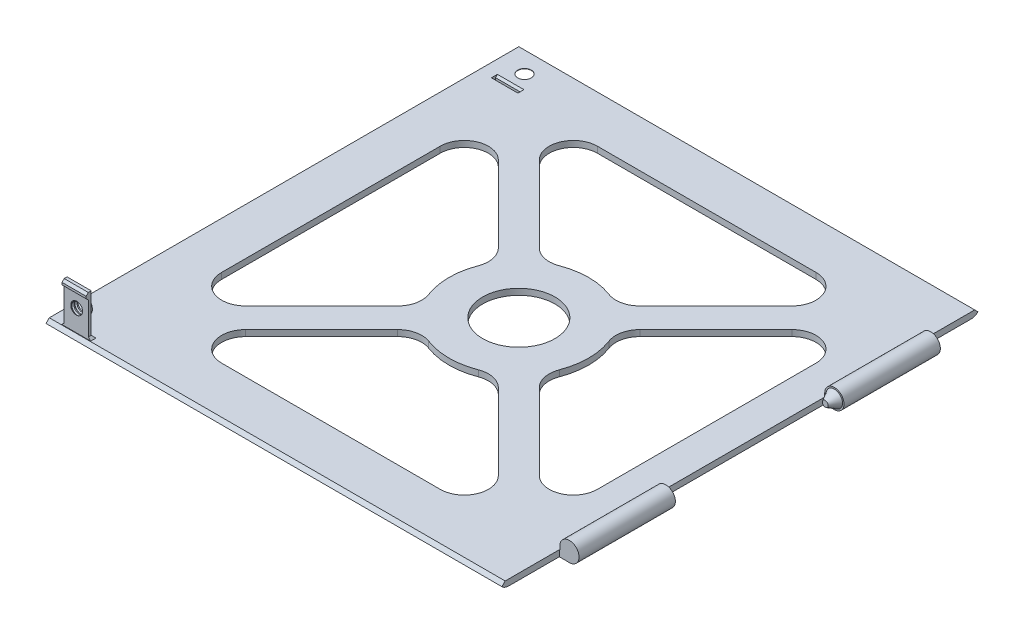
SolidWorks part; units mm, degrees
material "6061 Alloy"
ref_plane "Front Plane" through (0, 0, 0) normal (0, 0, 1) x (1, 0, 0)
ref_plane "Top Plane" through (0, 0, 0) normal (0, 1, 0) x (1, 0, 0)
ref_plane "Right Plane" through (0, 0, 0) normal (1, 0, 0) x (0, 0, -1)
sketch "X-Axis" plane through (0, 0, 0) normal (0, 1, 0) x (1, 0, 0)
  line L2 (-10, 0) -> (10, 0)
  point P3 (0, 0)
  dimension "D1" = 20
sketch "Y-Axis" plane through (0, 0, 0) normal (0, 1, 0) x (1, 0, 0)
  line L0 (0, -10) -> (0, 10)
  dimension "D1" = 20
sketch "Z-Axis" plane through (0, 0, 0) normal (1, 0, 0) x (0, 0, -1)
  line L0 (0, 10) -> (0, -10)
  line L1 (0, 55) -> (0, -55) construction
  point P5 (0, 0)
  dimension "D1" = 20
ref_axis "Axis1" through (0, 0, 0) along (0, 1, 0)
sketch "Sketch1" plane through (0, 0, 0) normal (0, 1, 0) x (1, 0, 0)
  line L0 (-10.4535, 14.6961) -> (-26.2218, 30.4645)
  line L1 (-46, -46) -> (46, -46) construction
  line L2 (-46, -46) -> (-46, 46) construction
  line L3 (-46, 46) -> (46, 46) construction
  line L4 (46, -46) -> (46, 46) construction
  line L5 (-46, -46) -> (46, 46) construction
  line L6 (-46, 46) -> (46, -46) construction
  line L7 (-22.6863, 39) -> (22.6863, 39)
  line L8 (26.2218, 30.4645) -> (10.4535, 14.6961)
  line L9 (30.4645, -26.2218) -> (14.6961, -10.4535)
  line L10 (14.6961, 10.4535) -> (30.4645, 26.2218)
  line L11 (39, 22.6863) -> (39, -22.6863)
  line L12 (-26.2218, -30.4645) -> (-10.4535, -14.6961)
  line L13 (10.4535, -14.6961) -> (26.2218, -30.4645)
  line L14 (22.6863, -39) -> (-22.6863, -39)
  line L15 (-30.4645, 26.2218) -> (-14.6961, 10.4535)
  line L16 (-14.6961, -10.4535) -> (-30.4645, -26.2218)
  line L17 (-39, -22.6863) -> (-39, 22.6863)
  line L19 (46, -50) -> (-46, -50)
  line L20 (46, -50) -> (46, 50)
  line L21 (46, 50) -> (-46, 50)
  line L22 (-46, -50) -> (-46, 50)
  line L23 (46, -50) -> (-46, 50) construction
  line L24 (46, 50) -> (-46, -50) construction
  circle A0 centre (0, 0) radius 7.5
  arc A1 (-5.1441, 13.5569) -> (5.1441, 13.5569) centre (0, 0) cw
  arc A2 (-5.1441, 13.5569) -> (-10.4535, 14.6961) centre (-6.9179, 18.2316) cw
  arc A3 (5.1441, 13.5569) -> (10.4535, 14.6961) centre (6.9179, 18.2316) ccw
  arc A4 (22.6863, 39) -> (26.2218, 30.4645) centre (22.6863, 34) cw
  arc A5 (-26.2218, 30.4645) -> (-22.6863, 39) centre (-22.6863, 34) cw
  arc A6 (13.5569, -5.1441) -> (14.6961, -10.4535) centre (18.2316, -6.9179) ccw
  arc A7 (13.5569, 5.1441) -> (13.5569, -5.1441) centre (0, 0) cw
  arc A8 (13.5569, 5.1441) -> (14.6961, 10.4535) centre (18.2316, 6.9179) cw
  arc A9 (30.4645, 26.2218) -> (39, 22.6863) centre (34, 22.6863) cw
  arc A10 (39, -22.6863) -> (30.4645, -26.2218) centre (34, -22.6863) cw
  arc A11 (-5.1441, -13.5569) -> (-10.4535, -14.6961) centre (-6.9179, -18.2316) ccw
  arc A12 (5.1441, -13.5569) -> (-5.1441, -13.5569) centre (0, 0) cw
  arc A13 (5.1441, -13.5569) -> (10.4535, -14.6961) centre (6.9179, -18.2316) cw
  arc A14 (26.2218, -30.4645) -> (22.6863, -39) centre (22.6863, -34) cw
  arc A15 (-22.6863, -39) -> (-26.2218, -30.4645) centre (-22.6863, -34) cw
  arc A16 (-13.5569, 5.1441) -> (-14.6961, 10.4535) centre (-18.2316, 6.9179) ccw
  arc A17 (-13.5569, -5.1441) -> (-13.5569, 5.1441) centre (0, 0) cw
  arc A18 (-13.5569, -5.1441) -> (-14.6961, -10.4535) centre (-18.2316, -6.9179) cw
  arc A19 (-30.4645, -26.2218) -> (-39, -22.6863) centre (-34, -22.6863) cw
  arc A20 (-39, 22.6863) -> (-30.4645, 26.2218) centre (-34, 22.6863) cw
  point P0 (0, 0)
  point P59 (0, 0)
  dimension "D3" = 15
  dimension "D6" = 7
  dimension "D8" = 5
  dimension "D1" = 92
  dimension "D2" = 92
  dimension "D4" = 6
  dimension "D5" = 6
  dimension "D7" = 39
  dimension "D10" = 100
  dimension "D9" = 4
extrude "Boss-Extrude1" add sketch "Sketch1" along normal blind 1.27
ref_plane "Plane3" through (0, 0, 17.5) normal (0, 0, 1) x (1, 0, 0)
sketch "Sketch6" plane through (0, 0, 17.5) normal (0, 0, 1) x (1, 0, 0)
  line L0 (46, 2) -> (46, 0)
  line L1 (46, 0) -> (48, 0)
  line L2 (0, 0) -> (0, 69.0457) construction
  arc A0 (46, 2) -> (48, 0) centre (48, 2) cw
  dimension "D1" = 50
extrude "Boss-Extrude3" add sketch "Sketch6" along normal blind 20
mirror "Mirror1" about plane through (0, 0, 0) normal (0, 0, 1) of "Boss-Extrude3"
sketch "Sketch16" plane through (0, 0, 17.5) normal (0, 0, -1) x (-1, 0, 0)
  circle A0 centre (-48, 2) radius 1.75
  dimension "D1" = 3.5
sketch "Sketch17" plane through (0, 0, -17.5) normal (0, 0, 1) x (1, 0, 0)
  circle A0 centre (48, 2) radius 1.7
  dimension "D1" = 3.4
extrude "Cut-Extrude5" cut sketch "Sketch16" against normal blind 2 draft 30 contours A0
extrude "Boss-Extrude7" add sketch "Sketch17" along normal blind 1.9 draft 30
sketch "Sketch23" plane through (0, 1.27, 0) normal (0, 1, 0) x (1, 0, 0)
  line L1 (-46, 50) -> (-49.5, 50)
  line L2 (-46, 50) -> (-46, -50)
  line L3 (-46, -50) -> (-49.5, -50)
  line L4 (-49.5, 50) -> (-49.5, -50)
  line L5 (50, 17.5) -> (50, 37.5) construction
  dimension "D1" = 99.5
extrude "Boss-Extrude9" add sketch "Sketch23" against normal up to surface (1.27 mm away) up to face at (0, 0, 24.6467)
sketch "Sketch21" plane through (46, 0, 0) normal (1, 0, 0) x (0, 0, -1)
  line L0 (-50, 0) -> (-47.5953, 2.4047) construction
  line L3 (-50, 0) -> (-37.5, 0) construction
  line L4 (-50, 1.27) -> (-50, 0) construction
  line L5 (-50, 1.27) -> (-37.5, 1.27) construction
  arc A0 (-50, 2) -> (-48, 0) centre (-48, 2) ccw
  dimension "D2" = 2
  dimension "D1" = 45
sketch "Sketch22" plane through (46, 0, 0) normal (1, 0, 0) x (0, 0, -1)
  line L0 (-48, 2) -> (-50.6263, -0.6263)
  line L2 (-50, 1.27) -> (-37.5, 1.27) construction
  point P0 (-48, 2)
  dimension "D1" = 45
extrude "Cut-Extrude7" cut sketch "Sketch22" against normal through all and the other way through all flip side to cut
extrude "Cut-Extrude8" cut sketch "Sketch21" against normal through all and the other way through all flip side to cut
sketch "Sketch24" plane through (0, 1.27, 0) normal (0, 1, 0) x (1, 0, 0)
  line L0 (46, -37.5) -> (50, -37.5) construction
  line L1 (46, -49.4142) -> (45.9, -49.4142)
  line L2 (46, -49.4142) -> (46, -37.5)
  line L3 (46, -37.5) -> (45.9, -37.5)
  line L4 (45.9, -49.4142) -> (45.9, -37.5)
  dimension "D1" = 0.1
extrude "Cut-Extrude9" cut sketch "Sketch24" against normal through all
mirror "Mirror2" about plane through (0, 0, 0) normal (0, 0, 1) of "Cut-Extrude8", "Cut-Extrude9", "Cut-Extrude7"
sketch "Sketch25" plane through (0, 1.27, 0) normal (0, 1, 0) x (1, 0, 0)
  line L1 (-49.5, -49.4142) -> (-48.73, -49.4142)
  line L2 (-49.5, -49.4142) -> (-49.5, -37.1142)
  line L3 (-49.5, -37.1142) -> (-48.73, -37.1142)
  line L4 (-48.73, -49.4142) -> (-48.73, -37.1142)
  line L5 (-49.5, 49.4142) -> (-48.73, 49.4142)
  line L6 (-49.5, 49.4142) -> (-49.5, 37.1142)
  line L7 (-49.5, 37.1142) -> (-48.73, 37.1142)
  line L8 (-48.73, 49.4142) -> (-48.73, 37.1142)
  dimension "D1" = 0.77
  dimension "D2" = 12.3
extrude "Cut-Extrude10" cut sketch "Sketch25" against normal through all
sketch "Sketch27" plane through (0, 1.27, 0) normal (0, 1, 0) x (1, 0, 0)
  line L1 (-45.73, -48.03) -> (-40.73, -48.03)
  line L2 (-45.73, -48.03) -> (-45.73, -48.63)
  line L3 (-45.73, -48.63) -> (-40.73, -48.63)
  line L4 (-40.73, -48.03) -> (-40.73, -48.63)
  line L5 (-48.73, -48.73) -> (-48.73, -37.1142) construction
  line L6 (45.9, -48.73) -> (-48.73, -48.73) construction
  dimension "D1" = 0.6
  dimension "D2" = 5
  dimension "D3" = 3
  dimension "D4" = 0.1
extrude "Boss-Extrude11" add sketch "Sketch27" along normal blind 8.5
sketch "Sketch28" plane through (-45.73, 0, 0) normal (-1, 0, 0) x (0, 0, 1)
  line L0 (48.63, 9.77) -> (49.0892, 9.3108)
  line L1 (49.0892, 9.3108) -> (49.0892, 8.8608)
  line L2 (49.0892, 8.8608) -> (48.63, 8.4016)
  line L3 (48.63, 9.77) -> (48.63, 1.27) construction
  line L4 (48.63, 8.4016) -> (48.63, 9.77)
  line L5 (48.03, 9.77) -> (48.63, 9.77) construction
  point P3 (49.0892, 9.0858)
  dimension "D1" = 0.45
  dimension "D2" = 0.6842
  dimension "D3" = 45
  dimension "D4" = 45
  dimension "D5" = 8.5
extrude "Boss-Extrude12" add sketch "Sketch28" against normal up to surface (5 mm away) up to face at (-40.73, 5.52, 48.33)
sketch "Sketch29" plane through (0, 1.27, 0) normal (0, 1, 0) x (1, 0, 0)
  line L1 (-45.98, 41.1392) -> (-40.48, 41.1392)
  line L2 (-45.98, 41.1392) -> (-45.98, 40.6892)
  line L3 (-45.98, 40.6892) -> (-40.48, 40.6892)
  line L4 (-40.48, 41.1392) -> (-40.48, 40.6892)
  line L8 (-40.73, -48.03) -> (-45.73, -48.03) construction
  line L9 (45.9, 49.4142) -> (-48.73, 49.4142) construction
  point P6 (-43.23, -48.03)
  point P7 (-45.98, 40.9142)
  point P11 (-43.23, 40.6892)
  dimension "D1" = 0.45
  dimension "D2" = 8.5
  dimension "D3" = 5.5
  dimension "D4" = 45.98
extrude "Cut-Extrude11" cut sketch "Sketch29" against normal through all
chamfer "Chamfer1" distance 0.4 angle 45 2 edges at (-43.23, 1.27, -40.6892) (-43.23, 1.27, -41.1392)
chamfer "Chamfer2" distance 0.5 angle 45 3 edges at (-40.73, 1.27, 48.33) (-43.23, 1.27, 48.03) (-45.73, 1.27, 48.33)
sketch "Sketch30" plane through (0, 0, 48.03) normal (0, 0, -1) x (-1, 0, 0)
  line L0 (40.73, 9.77) -> (45.73, 9.77) construction
  line L4 (40.73, 9.3108) -> (40.73, 8.8608) construction
  circle A0 centre (43.23, 5.5858) radius 1.75
  point P4 (43.23, 9.77)
  point P5 (40.73, 9.0858)
  dimension "D1" = 3.5
  dimension "D2" = 3.5
extrude "Boss-Extrude13" add sketch "Sketch30" along normal blind 1
hole_wizard "Tap Drill for #4-40 Tap1" positions "Sketch34" profile "Sketch33" hole size "#4-40" standard "ANSI Inch" end condition through all
sketch "Sketch34" plane through (0, 0, 47.03) normal (0, 0, -1) x (-1, 0, 0)
  point P0 (43.23, 5.5858)
sketch "Sketch33" plane through (-43.23, 5.5858, 47.03) normal (1, 0, 0) x (0, 1, 0)
  line L0 (0, 0) -> (0, 2.3842)
  line L1 (0, 2.3842) -> (1.1303, 2.3842)
  line L2 (1.1303, 2.3842) -> (1.1303, 0)
  line L5 (1.1303, 0) -> (0, 0)
  line L11 (0, -6.35) -> (0, 107.95) construction
  dimension "Thru Hole Dia." = 2.2606
  dimension "Thru Hole Depth" = 2.3842
ref_plane "Plane5" through (0, 0, 45.03) normal (0, 0, -1) x (-1, 0, 0)
sketch "Sketch35" plane through (0, 0, 45.03) normal (0, 0, -1) x (-1, 0, 0)
  circle A0 centre (43.23, 5.5858) radius 1.1303 construction
  circle A1 centre (43.23, 5.5858) radius 1.1303
curve "Helix/Spiral1" pitch 0.635 height 9.525 radius 1.1303 centre (-43.23, 5.5858, 45.03) axis (0, 0, 1) start towards (-1, 0, 0)
ref_plane "Plane6" through (-44.3603, 5.5858, 45.03) normal (0, -0.996, 0.0891) x (-1, 0, 0)
ref_axis "Axis2" through (-43.23, 5.5858, 47.03) along (0, 0, 1)
sketch "Sketch37" plane through (-44.3603, 5.5858, 45.03) normal (0, -0.996, 0.0891) x (-1, 0, 0)
  line L0 (0.2921, 0.0397) -> (0.2921, -0.0397)
  line L1 (0.2921, -0.0397) -> (-0.1079, -0.2706)
  line L2 (-0.1079, -0.2706) -> (-0.1079, 0.2706)
  line L3 (-0.1079, 0.2706) -> (0.2921, 0.0397)
  line L7 (-1.1303, -1.9921) -> (-1.1303, -2.9881) construction
  point P6 (0.2921, 0)
  point P7 (0, 0)
  dimension "D1" = 1.4224
  dimension "D2" = 60
  dimension "D3" = 60
  dimension "D4" = 0.0794
  dimension "D5" = 0.4
sweep "Cut-Sweep1" cut profiles "Sketch37" path "Helix/Spiral1"
sketch "Sketch32" plane through (0, 1.27, 0) normal (0, 1, 0) x (1, 0, 0)
  line L0 (-45.98, 40.6892) -> (-40.48, 40.6892) construction
  line L2 (-45.98, 41.5392) -> (-45.98, 40.2892) construction
  circle A0 centre (-43.23, 44.4142) radius 1.4046
  point P4 (-43.23, 40.6892)
  point P5 (-45.98, 40.9142)
  dimension "D1" = 2.8092
  dimension "D2" = 3.5
extrude "Cut-Extrude13" cut sketch "Sketch32" against normal through all
sketch "Sketch38" plane through (0, 1.27, 0) normal (0, 1, 0) x (1, 0, 0)
  line L1 (-49.5, 37.1142) -> (-48.73, 37.1142)
  line L2 (-49.5, 37.1142) -> (-49.5, -37.1142)
  line L3 (-49.5, -37.1142) -> (-48.73, -37.1142)
  line L4 (-48.73, 37.1142) -> (-48.73, -37.1142)
extrude "Cut-Extrude14" cut sketch "Sketch38" against normal through all
ref_axis "Axis3" through (-43.23, 0, -44.4142) along (0, 1, 0)
ref_plane "Plane7" through (-43.23, 0, 0) normal (-1, 0, 0) x (0, 0, 1)
sketch "Sketch39" plane through (-43.23, 0, 0) normal (-1, 0, 0) x (0, 0, 1)
  line L0 (-47.7162, 0) -> (-46.6785, 1.1938)
  line L1 (-46.6785, 1.1938) -> (-44.4142, 1.1938)
  line L2 (-44.4142, 0) -> (-44.4142, 1.27) construction
  line L3 (-44.4142, 1.1938) -> (-44.4142, 0)
  line L5 (-44.4142, 0) -> (-47.7162, 0)
  line L6 (-44.4142, 1.1938) -> (-44.4142, 2.1139) construction
  line L7 (48, 0) -> (-48, 0) construction
  dimension "D1" = 49
  dimension "D2" = 6.604
  dimension "D3" = 1.1938
revolve "Cut-Revolve1" cut sketch "Sketch39" angle 360 about L6
equation "\"D2@Sketch32\"=\"D2@Sketch30\""
equation "\"D2@Sketch29\"=\"D1@Boss-Extrude11\""
